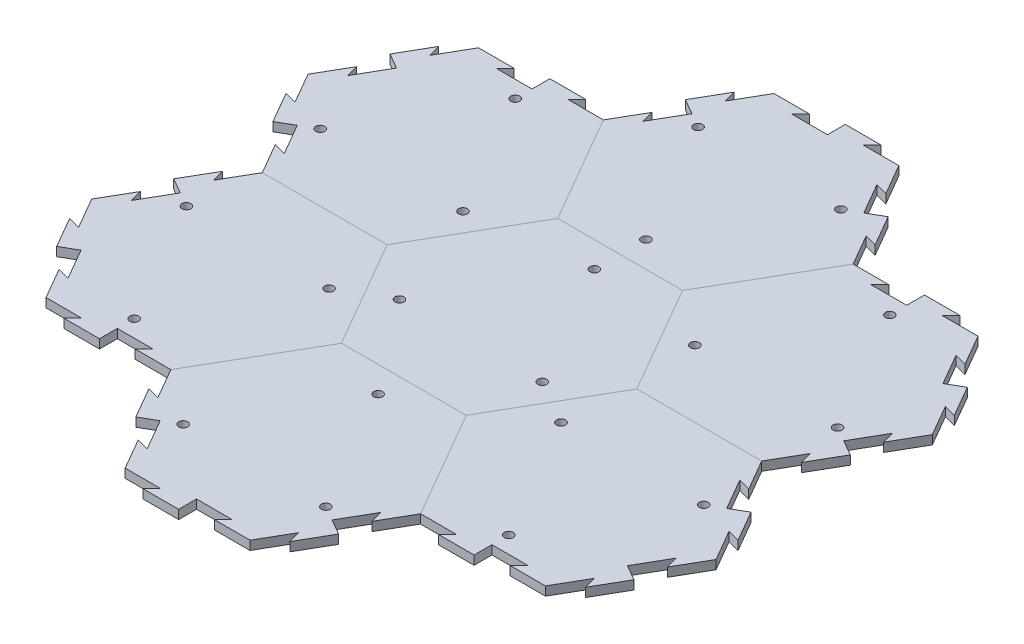
SolidWorks part; units mm, degrees
material "Cedar"
ref_plane "Front Plane" through (0, 0, 0) normal (0, 0, 1) x (1, 0, 0)
ref_plane "Top Plane" through (0, 0, 0) normal (0, 1, 0) x (1, 0, 0)
ref_plane "Right Plane" through (0, 0, 0) normal (1, 0, 0) x (0, 0, -1)
sketch "Sketch1" plane through (0, 0, 0) normal (0, 1, 0) x (1, 0, 0)
  line L0 (0, 0) -> (88.9, 0) construction
  line L1 (88.9, 0) -> (44.45, 76.9897)
  line L2 (44.45, 76.9897) -> (-44.45, 76.9897)
  line L3 (-44.45, 76.9897) -> (-88.9, 0)
  line L4 (-88.9, 0) -> (-44.45, -76.9897)
  line L5 (-44.45, -76.9897) -> (44.45, -76.9897)
  line L6 (44.45, -76.9897) -> (88.9, 0)
  circle A0 centre (0, 0) radius 76.9897 construction
  dimension "D1" = 88.9
extrude "Boss-Extrude1" add sketch "Sketch1" against normal blind 6.35
sketch "Sketch2" plane through (0, 0, 0) normal (0, 1, 0) x (1, 0, 0)
  point P1 (0, 0)
ref_axis "Axis1" through (0, 0, 0) along (0, 1, 0)
sketch "Sketch9" plane through (0, 0, 0) normal (0, 1, 0) x (1, 0, 0)
  line L1 (50.8, -29.3294) -> (0, 58.6588) construction
  line L2 (0, 58.6588) -> (-50.8, -29.3294) construction
  line L3 (-50.8, -29.3294) -> (50.8, -29.3294) construction
  circle A0 centre (0, 0) radius 29.3294 construction
  circle A1 centre (-50.8, -29.3294) radius 3.175
  dimension "D2" = 6.35
  dimension "D1" = 101.6
extrude "Cut-Extrude3" cut sketch "Sketch9" against normal through all
pattern_circular "CirPattern6" count 3 over 360 about axis through (0, 0, 0) along (0, 1, 0) of "Cut-Extrude3"
mirror "Mirror1" about plane through (44.45, -6.35, 76.9897) normal (0.866, 0, 0.5) of bodies 121 101
sketch "Sketch5" plane through (0, 0, 0) normal (0, 1, 0) x (1, 0, 0)
  line L0 (177.8, 0) -> (190.5, -21.997) construction
  line L1 (177.8, 0) -> (222.25, -76.9897) construction
  line L2 (190.5, -21.997) -> (181.8257, -19.6728)
  line L3 (181.8257, -19.6728) -> (194.5257, -41.6698)
  line L4 (194.5257, -41.6698) -> (200.025, -38.4948)
  line L5 (177.8, 0) -> (222.25, -76.9897) construction
  line L6 (190.5, -21.997) -> (200.025, -38.4948)
  dimension "D1" = 45
  dimension "D2" = 6.35
sketch "Sketch6" plane through (0, 0, 0) normal (0, 1, 0) x (1, 0, 0)
  line L0 (44.45, -76.9897) -> (222.25, -76.9897) construction
  point P4 (133.35, -76.9897)
ref_axis "Axis3" through (133.35, 0, 76.9897) along (0, 1, 0)
extrude "Cut-Extrude2" cut sketch "Sketch5" against normal through all
sketch "Sketch7" plane through (0, 0, 0) normal (0, 1, 0) x (1, 0, 0)
  line L0 (200.025, -38.4948) -> (222.25, -76.9897) construction
  line L1 (200.025, -38.4948) -> (222.25, -76.9897) construction
  line L2 (200.025, -38.4948) -> (205.5243, -35.3198)
  line L3 (205.5243, -35.3198) -> (218.2243, -57.3169)
  line L4 (218.2243, -57.3169) -> (209.55, -54.9926)
  line L5 (209.55, -54.9926) -> (200.025, -38.4948)
  line L6 (209.55, -54.9926) -> (222.25, -76.9897) construction
  line L7 (209.55, -54.9926) -> (222.25, -76.9897) construction
  dimension "D1" = 45
  dimension "D2" = 6.35
extrude "Boss-Extrude3" add sketch "Sketch7" against normal up to surface (6.35 mm away) up to face at (82.55, -6.35, 44.4853)
pattern_circular "CirPattern3" count 3 every 60 about axis through (133.35, 0, 76.9897) along (0, 1, 0) of "Cut-Extrude2", "Boss-Extrude3" reverse direction yes
pattern_circular "CirPattern5" count 6 over 360 about axis through (0, 0, 0) along (0, 1, 0) of bodies 113
